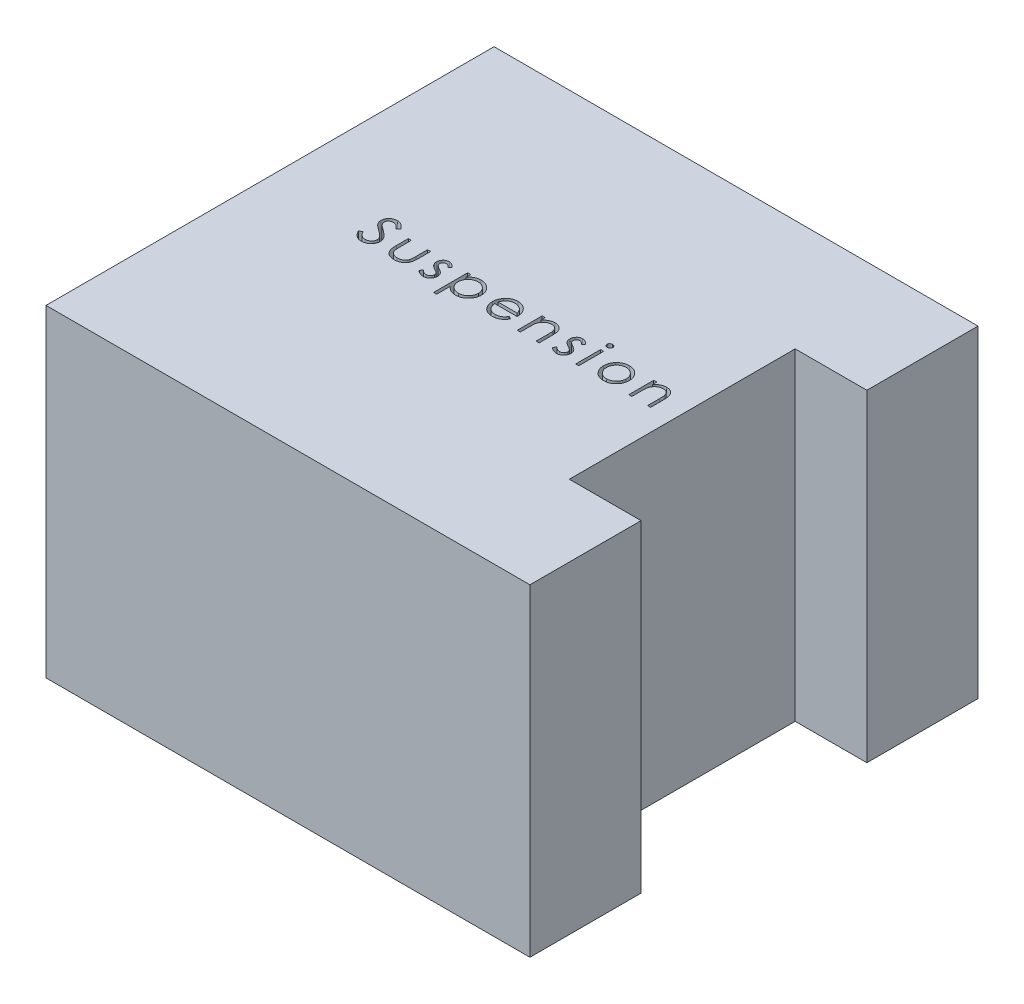
SolidWorks part; units mm, degrees
ref_plane "정면" through (0, 0, 0) normal (0, 0, 1) x (1, 0, 0)
ref_plane "윗면" through (0, 0, 0) normal (0, 1, 0) x (1, 0, 0)
ref_plane "우측면" through (0, 0, 0) normal (1, 0, 0) x (0, 0, -1)
sketch "Sketch1" plane through (0, 0, 0) normal (0, 1, 0) x (1, 0, 0)
  line L1 (135, -125) -> (-135, -125)
  line L2 (135, -125) -> (135, 125)
  line L3 (135, 125) -> (-135, 125)
  line L4 (-135, -125) -> (-135, 125)
  line L5 (135, -125) -> (-135, 125) construction
  line L6 (135, 125) -> (-135, -125) construction
  point P0 (0, 0)
  dimension "D1" = 250
  dimension "D2" = 270
extrude "Boss-Extrude1" add sketch "Sketch1" along normal blind 90 and the other way blind 90
sketch "Sketch2" plane through (0, 90, 0) normal (0, 1, 0) x (1, 0, 0)
  text T0 "Suspension" font "Century Gothic" height in points 72
extrude "Cut-Extrude1" cut sketch "Sketch2" against normal blind 50
sketch "Sketch3" plane through (0, 90, 0) normal (0, 1, 0) x (1, 0, 0)
  line L0 (135, -125) -> (135, 125) construction
  line L1 (94.9953, -63) -> (175.0047, -63)
  line L2 (94.9953, -63) -> (94.9953, 63)
  line L3 (94.9953, 63) -> (175.0047, 63)
  line L4 (175.0047, -63) -> (175.0047, 63)
  line L5 (94.9953, -63) -> (175.0047, 63) construction
  line L6 (94.9953, 63) -> (175.0047, -63) construction
  point P0 (135, 0)
  dimension "D1" = 126
extrude "Cut-Extrude2" cut sketch "Sketch3" against normal through all
